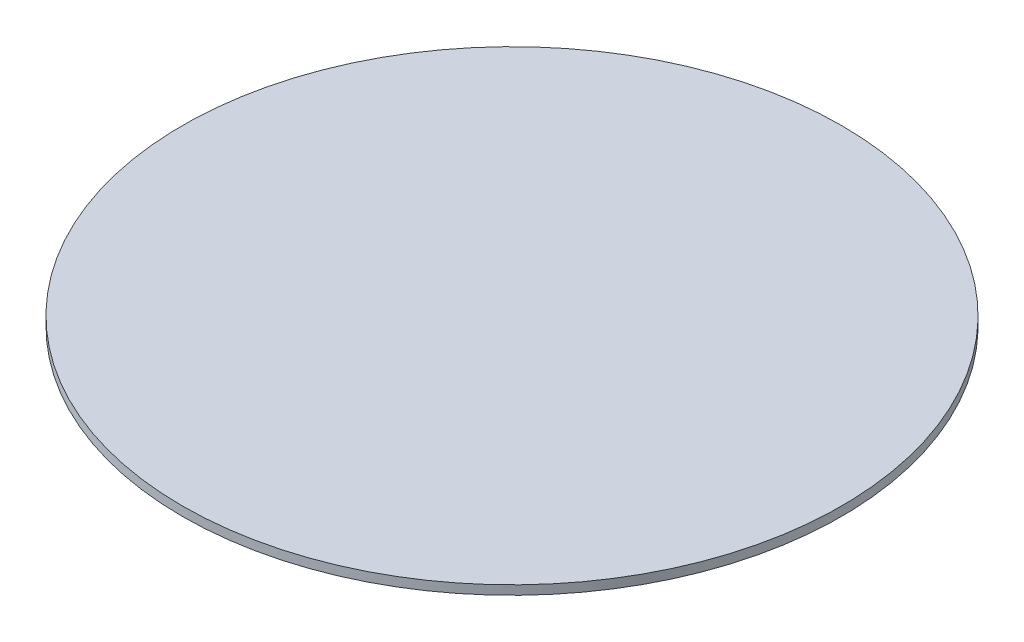
SolidWorks part; units mm, degrees
ref_plane "前视基准面" through (0, 0, 0) normal (0, 0, 1) x (1, 0, 0)
ref_plane "上视基准面" through (0, 0, 0) normal (0, 1, 0) x (1, 0, 0)
ref_plane "右视基准面" through (0, 0, 0) normal (1, 0, 0) x (0, 0, -1)
sketch "草图2" plane through (0, 0, 0) normal (0, 1, 0) x (1, 0, 0)
  circle A0 centre (0, 0) radius 72.5
  dimension "D1" = 145
extrude "凸台-拉伸1" add sketch "草图2" along normal blind 2
